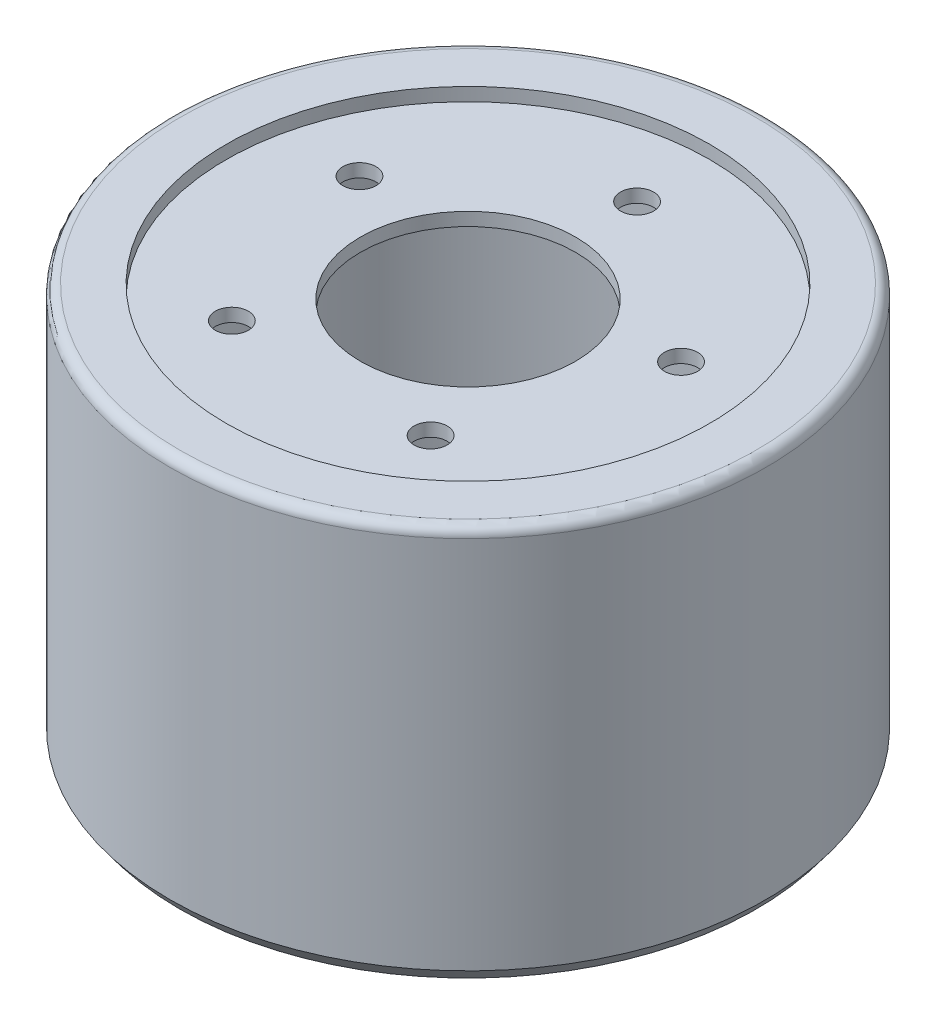
SolidWorks part; units mm, degrees
ref_plane "Front Plane" through (0, 0, 0) normal (0, 0, 1) x (1, 0, 0)
ref_plane "Top Plane" through (0, 0, 0) normal (0, 1, 0) x (1, 0, 0)
ref_plane "Right Plane" through (0, 0, 0) normal (1, 0, 0) x (0, 0, -1)
sketch "Sketch3" plane through (0, 0, 0) normal (0, 1, 0) x (1, 0, 0)
  circle A0 centre (0, 0) radius 45
  circle A1 centre (0, 0) radius 36.5
  circle A2 centre (0, 0) radius 16.25
  circle A3 centre (0, 0) radius 25.52 construction
  circle A10 centre (0, 25.52) radius 2.5
  circle A18 centre (24.271, 7.8861) radius 2.5
  circle A19 centre (15.0003, -20.6461) radius 2.5
  circle A20 centre (-15.0003, -20.6461) radius 2.5
  circle A21 centre (-24.271, 7.8861) radius 2.5
  point P8 (-24.2707, 7.887)
  point P9 (15.0314, -20.6235)
  point P18 (1.7205, -1.25)
  point P19 (1.3626, -0.99)
  point P20 (0, 0)
  point P21 (0, 0)
  point P22 (0, 0)
  dimension "D1" = 32.5
  dimension "D2" = 73
  dimension "D3" = 90
  dimension "D4" = 51.04
  dimension "D6" = 5
  dimension "D5" = 5
extrude "Boss-Extrude1" add sketch "Sketch3" along normal blind 60 contours A0 A1 region at (-43.7272, 0, 0)
fillet "Fillet1" radius 1.5 1 edges at (0, 60, 45)
extrude "Boss-Extrude3" add sketch "Sketch3<6>" along normal blind 2 from offset 56 contours A3 A2 | A1 A3 region at (-35.4676, 0, 0)
sketch "Sketch3<6>" plane through (0, 0, 0) normal (0, 1, 0) x (1, 0, 0) same geometry as "Sketch3"
chamfer "Chamfer2" distance 1.5 distance2 2 1 edges at (0, 0, 45) first distance on face at (0, 0, 36.5)
